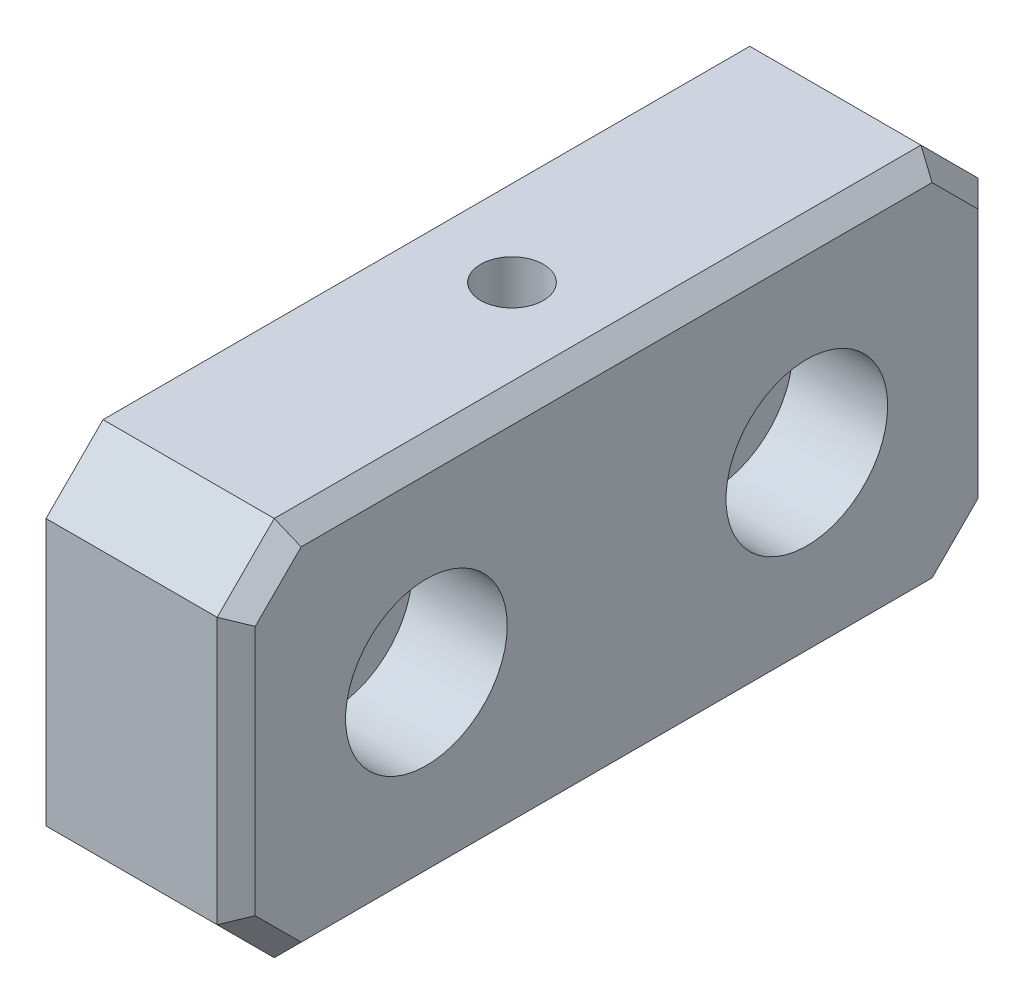
SolidWorks part; units mm, degrees
ref_plane "Front Plane" through (0, 0, 0) normal (0, 0, 1) x (1, 0, 0)
ref_plane "Top Plane" through (0, 0, 0) normal (0, 1, 0) x (1, 0, 0)
ref_plane "Right Plane" through (0, 0, 0) normal (1, 0, 0) x (0, 0, -1)
sketch "Sketch1" plane through (0, 0, 0) normal (1, 0, 0) x (0, 0, -1)
  line L1 (-20, 10) -> (20, 10)
  line L2 (-20, 10) -> (-20, -10)
  line L3 (-20, -10) -> (20, -10)
  line L4 (20, 10) -> (20, -10)
  line L5 (-20, 10) -> (20, -10) construction
  line L6 (-20, -10) -> (20, 10) construction
  point P0 (0, 0)
  dimension "D1" = 40
  dimension "D2" = 20
extrude "Boss-Extrude1" add sketch "Sketch1" along normal blind 10
chamfer "Chamfer1" distance 3 angle 45 4 edges at (5, 10, -20) (5, -10, -20) (5, -10, 20) (5, 10, 20)
chamfer "Chamfer2" distance 1 angle 45 8 edges at (10, -8.5, -18.5) (10, -10, 0) (10, -8.5, 18.5) (10, 0, 20) (10, 8.5, 18.5) (10, 10, 0) (10, 8.5, -18.5) (10, 0, -20)
sketch "Sketch2" plane through (10, 0, 0) normal (1, 0, 0) x (0, 0, -1)
  line L0 (-20, 0) -> (20, 0)
  line L1 (-20, -7) -> (-20, 7) construction
  line L2 (20, 7) -> (20, -7) construction
  line L3 (0, 10) -> (0, -10)
  line L4 (-17, 10) -> (17, 10) construction
  line L5 (17, -10) -> (-17, -10) construction
  circle A0 centre (-10, 0) radius 2.25
  circle A1 centre (-10, 0) radius 4.25
  circle A2 centre (10, 0) radius 2.25
  circle A3 centre (10, 0) radius 4.25
  dimension "D1" = 10
extrude "Cut-Extrude1" cut sketch "Sketch2" against normal blind 10 contours L0 A0 | L0 A0 | A2 L0 | A2 L0 region at (10, -0.9549, 10) region at (10, 0.9549, 10) region at (10, 0.9549, -10) region at (10, -0.9549, -10)
extrude "Cut-Extrude2" cut sketch "Sketch2<3>" against normal blind 5 contours L0 A1 A0 | L0 A1 A0 | A3 L0 A2 | A3 L0 A2 region at (10, 2.345, 10) region at (10, -0.095, 6.75) region at (10, 4.155, -10) region at (10, -0.095, -6.75)
sketch "Sketch2<3>" plane through (10, 0, 0) normal (1, 0, 0) x (0, 0, -1) same geometry as "Sketch2"
sketch "Sketch3" plane through (0, 10, 0) normal (0, 1, 0) x (1, 0, 0)
  circle A0 centre (4.5, 0) radius 1.65
extrude "Cut-Extrude3" cut sketch "Sketch3" against normal blind 5
